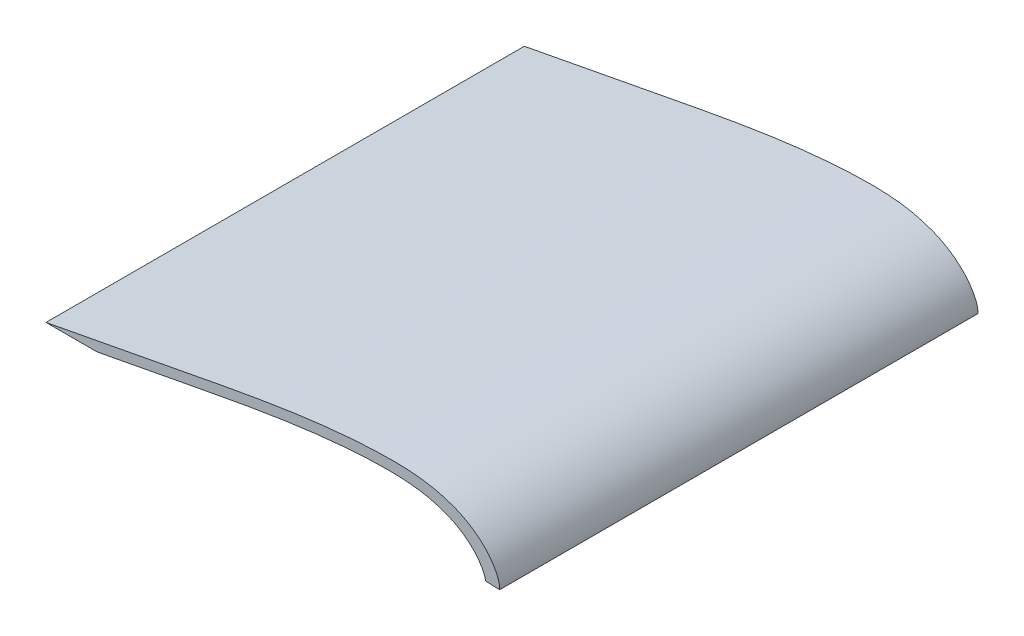
SolidWorks part; units mm, degrees
ref_plane "Front Plane" through (0, 0, 0) normal (0, 0, 1) x (1, 0, 0)
ref_plane "Top Plane" through (0, 0, 0) normal (0, 1, 0) x (1, 0, 0)
ref_plane "Right Plane" through (0, 0, 0) normal (1, 0, 0) x (0, 0, -1)
sketch "Sketch3" plane through (0, 0, 0) normal (0, 0, 1) x (1, 0, 0)
  line L0 (-35.4155, 0.9786) -> (-46.127, 0.9786)
  line L1 (45.7527, 0.1003) -> (48.7207, 0)
  line L2 (48.7207, 0) -> (-34.4545, 0) construction
  spline S0 degree 3 poles (48.7207, 0) (48.7413, 1.212) (48.0464, 2.8572) (46.8151, 4.7839) (45.4925, 6.3024) (43.8268, 7.7408) (41.4946, 9.2643) (38.1681, 10.7172) (33.7887, 11.8315) (28.7294, 12.2559) (23.717, 12.2188) (17.039, 11.8576) (8.6903, 10.9743) (-1.3041, 9.4479) (-11.2877, 7.6112) (-21.2786, 5.6967) (-34.613, 3.1689) (-44.6124, 1.2656) (-51.2793, 0) knots 0 0 0 0 0.032627 0.049883 0.064276 0.089251 0.111668 0.142584 0.191136 0.23834 0.285329 0.332382 0.426847 0.521876 0.617364 0.713023 0.808682 1 1 1 1
  spline S1 degree 3 poles (-35.4155, 0.9786) (-31.9007, 1.6464) (-28.3857, 2.3126) (-21.3563, 3.6489) (-17.8426, 4.3227) (-10.8123, 5.6541) (-7.2961, 6.3141) (-0.2462, 7.5388) (3.2897, 8.1009) (10.3826, 9.0556) (13.9397, 9.4499) (19.2948, 9.846) (21.0805, 9.9456) (24.6541, 10.0538) (26.4418, 10.0626) (29.1266, 9.9312) (30.0211, 9.8625) (31.7935, 9.6561) (32.6728, 9.5176) (34.415, 9.1542) (35.2779, 8.9305) (36.5587, 8.5235) (36.9845, 8.3756) (37.8235, 8.0564) (38.6499, 7.7134) (39.4456, 7.3119) (40.2226, 6.8751) (40.6019, 6.6392) (41.343, 6.1342) (41.7066, 5.8644) (42.4051, 5.299) (42.7404, 5.0027) (43.379, 4.3788) (43.6829, 4.0517) (44.2484, 3.3563) (44.5091, 2.9837) (44.8649, 2.4053) (44.978, 2.2096) (45.194, 1.8126) (45.2964, 1.6111) (45.4811, 1.1971) (45.5636, 0.9838) (45.6906, 0.5499) (45.7355, 0.3285) (45.7527, 0.1003) knots 0 0 0 0 0.125 0.125 0.25 0.25 0.375 0.375 0.5 0.5 0.625 0.625 0.6875 0.6875 0.75 0.75 0.78125 0.78125 0.8125 0.8125 0.84375 0.84375 0.859375 0.859375 0.875 0.890625 0.890625 0.90625 0.90625 0.921875 0.921875 0.9375 0.9375 0.953125 0.953125 0.96875 0.96875 0.976562 0.976562 0.984375 0.984375 0.992188 0.992188 1 1 1 1
  point P6 (0, 0)
extrude "Boss-Extrude1" add sketch "Sketch3" along normal mid plane 100 contours L0 S1 L1 S0 region at (-40.7712, 1.9349, 0)
sketch "Sketch4" plane through (0, 0, 0) normal (0, 1, 0) x (1, 0, 0)
  line L0 (48.7207, -50) -> (48.7207, 50) construction
  line L1 (48.7207, -50) -> (48.7207, 50)
  line L2 (48.7207, 0) -> (-13.2793, 0) construction
  circle A0 centre (-13.2793, 0) radius 4.9
  dimension "D1" = 9.8
  dimension "D2" = 62
extrude "Boss-Extrude2" add sketch "Sketch4" along normal up to surface and the other way blind 0.46 contours A0 region at (-13.2793, 0, 0) up to face at (-15.1234, 0.759, 0)
sketch "Sketch5" plane through (0, 0, 0) normal (0, 0, 1) x (1, 0, 0)
  line L1 (-8.3793, -0.46) -> (-8.3793, 6.1015) construction
  line L2 (-8.3793, -0.46) -> (-8.3793, 6.1015)
  line L3 (-18.1793, 4.2563) -> (-18.1793, -0.46) construction
  line L4 (-18.1793, 4.2563) -> (-18.1793, -0.46)
  spline S1 degree 3 poles (-525.0903, -2862.9343) (-687.8734, -106.1956) (-354.8821, -59.7534) (-21.3563, 3.6489) (-17.8426, 4.3227) (-10.8123, 5.6541) (-7.2961, 6.3141) (-0.2462, 7.5388) (3.2897, 8.1009) (10.3826, 9.0556) (13.9397, 9.4499) (19.2948, 9.846) (21.0805, 9.9456) (24.6541, 10.0538) (26.4418, 10.0626) (29.1266, 9.9312) (30.0211, 9.8625) (31.7935, 9.6561) (32.6728, 9.5176) (34.415, 9.1542) (35.2779, 8.9305) (36.5587, 8.5235) (36.9845, 8.3756) (37.8235, 8.0564) (38.6499, 7.7134) (39.4456, 7.3119) (40.2226, 6.8751) (40.6019, 6.6392) (41.343, 6.1342) (41.7066, 5.8644) (42.4051, 5.299) (42.7404, 5.0027) (43.379, 4.3788) (43.6829, 4.0517) (44.2484, 3.3563) (44.5091, 2.9837) (44.8649, 2.4053) (44.978, 2.2096) (45.194, 1.8126) (45.2964, 1.6111) (45.4811, 1.1971) (45.5636, 0.9838) (49.8278, -13.5819) (-27.1275, -47.71) (-2855.9649, -752.5254) knots -11.611785 -11.611785 -11.611785 -11.611785 0.125 0.125 0.25 0.25 0.375 0.375 0.5 0.5 0.625 0.625 0.6875 0.6875 0.75 0.75 0.78125 0.78125 0.8125 0.8125 0.84375 0.84375 0.859375 0.859375 0.875 0.890625 0.890625 0.90625 0.90625 0.921875 0.921875 0.9375 0.9375 0.953125 0.953125 0.96875 0.96875 0.976562 0.976562 0.984375 0.984375 0.992188 0.992188 1.508965 1.508965 1.508965 1.508965 only from (-35.4155, 0.9786) to (45.7527, 0.1003) construction
  spline S2 degree 3 poles (-35.4155, 0.9786) (-31.9007, 1.6464) (-28.3857, 2.3126) (-21.3563, 3.6489) (-17.8426, 4.3227) (-10.8123, 5.6541) (-7.2961, 6.3141) (-0.2462, 7.5388) (3.2897, 8.1009) (10.3826, 9.0556) (13.9397, 9.4499) (19.2948, 9.846) (21.0805, 9.9456) (24.6541, 10.0538) (26.4418, 10.0626) (29.1266, 9.9312) (30.0211, 9.8625) (31.7935, 9.6561) (32.6728, 9.5176) (34.415, 9.1542) (35.2779, 8.9305) (36.5587, 8.5235) (36.9845, 8.3756) (37.8235, 8.0564) (38.6499, 7.7134) (39.4456, 7.3119) (40.2226, 6.8751) (40.6019, 6.6392) (41.343, 6.1342) (41.7066, 5.8644) (42.4051, 5.299) (42.7404, 5.0027) (43.379, 4.3788) (43.6829, 4.0517) (44.2484, 3.3563) (44.5091, 2.9837) (44.8649, 2.4053) (44.978, 2.2096) (45.194, 1.8126) (45.2964, 1.6111) (45.4811, 1.1971) (45.5636, 0.9838) (45.6906, 0.5499) (45.7355, 0.3285) (45.7527, 0.1003) knots 0 0 0 0 0.125 0.125 0.25 0.25 0.375 0.375 0.5 0.5 0.625 0.625 0.6875 0.6875 0.75 0.75 0.78125 0.78125 0.8125 0.8125 0.84375 0.84375 0.859375 0.859375 0.875 0.890625 0.890625 0.90625 0.90625 0.921875 0.921875 0.9375 0.9375 0.953125 0.953125 0.96875 0.96875 0.976562 0.976562 0.984375 0.984375 0.992188 0.992188 1 1 1 1
  point P0 (-18.1793, 4.2563)
  point P1 (-18.1793, -0.46)
  point P5 (-8.3793, -0.46)
  dimension "D1" = 6.5615
  dimension "D2" = 4.7163
sketch "Sketch6" plane through (0, 0, 0) normal (0, 0, 1) x (1, 0, 0)
  line L0 (-18.1793, -0.46) -> (-8.3793, -0.46) construction
  line L1 (-18.1793, -0.46) -> (-8.3793, -0.46)
  line L2 (-13.2793, -0.46) -> (-13.2793, 3.54)
  line L3 (-13.2793, 3.54) -> (-10.2793, 3.54)
  line L4 (-10.2793, 3.54) -> (-10.2793, 1.54)
  line L5 (-10.2793, 1.54) -> (-11.7793, 1.54)
  line L6 (-11.7793, 1.54) -> (-11.7793, -0.46)
  point P2 (-13.2793, -0.46)
  dimension "D1" = 1.5
  dimension "D2" = 2
  dimension "D3" = 3
  dimension "D4" = 2
revolve "Cut-Revolve1" cut sketch "Sketch6" angle 360 about L2 region at (-12.0293, 1.8733, 0)
sketch "Sketch7" plane through (0, 0, 0) normal (0, 0, 1) x (1, 0, 0)
  line L0 (-18.1793, -0.46) -> (-8.3793, -0.46) construction
  line L1 (-18.1793, -0.46) -> (-8.3793, -0.46)
  line L2 (-13.2793, -0.46) -> (-13.2793, 1.54) construction
  line L3 (-16.2793, 1.54) -> (-10.2793, 1.54)
  line L4 (-14.2793, 0.54) -> (-12.2793, 0.54) construction
  line L5 (-14.2793, 1.54) -> (-14.2793, -0.46)
  line L6 (-12.2793, 1.54) -> (-12.2793, -0.46)
  line L7 (-16.2793, 1.54) -> (-16.2793, 3.04)
  line L8 (-16.2793, 3.04) -> (-10.2793, 3.04)
  line L9 (-10.2793, 3.04) -> (-10.2793, 1.54)
  point P7 (-13.2793, 1.54)
  point P10 (-13.2793, 0.54)
  dimension "D1" = 2
  dimension "D2" = 6
  dimension "D3" = 2
  dimension "D4" = 1.5
ref_plane "Plane1" through (-13.2793, 0, 0) normal (1, 0, 0) x (0, 0, -1)
sketch "Sketch8" plane through (-13.2793, 0, 0) normal (1, 0, 0) x (0, 0, -1)
  line L0 (-1.5, -0.46) -> (1.5, -0.46) construction
  line L1 (-1.5, -0.46) -> (1.5, -0.46)
  line L2 (-3, 3.54) -> (3, 3.54)
  line L3 (-3, 3.54) -> (3, 3.54) construction
  line L4 (-3, 3.54) -> (-3, 1.54)
  line L5 (3, 1.54) -> (-3, 1.54) construction
  line L6 (-3, 1.54) -> (-1, 1.54)
  line L7 (-1, 1.54) -> (-1, -0.46)
  line L8 (-1, -0.46) -> (1, -0.46)
  line L9 (1, -0.46) -> (1, 1.54)
  line L10 (1, 1.54) -> (3, 1.54)
  line L11 (3, 1.54) -> (3, 3.54)
  line L12 (1, 0.7183) -> (-1, 0.7183) construction
  line L14 (0, -0.46) -> (0, 1.54) construction
  point P17 (0, 0.7183)
  point P20 (0, 0)
  dimension "D1" = 2
  dimension "D2" = 2
extrude "Cut-Extrude2" cut sketch "Sketch8" against normal blind 5 contours L10 L11 L2 L4 L6 L7 L1 L9 region at (-13.2793, 2.04, 0)
sketch "Sketch13" plane through (0, 0, 50) normal (0, 0, 1) x (1, 0, 0)
  line L1 (45.7527, 0.1003) -> (48.7207, 0) construction
  line L2 (45.7527, 0.1003) -> (48.7207, 0)
sketch "Sketch14" plane through (0, 0, 50) normal (0, 0, 1) x (1, 0, 0)
  spline S0 degree 3 poles (-2870.1927, -688.3452) (26.4309, -61.9171) (59.7941, -15.5258) (46.8151, 4.7839) (45.4925, 6.3024) (43.8268, 7.7408) (41.4946, 9.2643) (38.1681, 10.7172) (33.7887, 11.8315) (28.7294, 12.2559) (23.717, 12.2188) (17.039, 11.8576) (8.6903, 10.9743) (-1.3041, 9.4479) (-11.2877, 7.6112) (-21.2786, 5.6967) (-506.1884, -86.23) (-984.3764, -194.629) (-1935.2759, 2100.805) knots -0.613276 -0.613276 -0.613276 -0.613276 0.032627 0.049883 0.064276 0.089251 0.111668 0.142584 0.191136 0.23834 0.285329 0.332382 0.426847 0.521876 0.617364 0.713023 0.808682 14.532028 14.532028 14.532028 14.532028 only from (48.7207, 0) to (-51.2793, 0) construction
  spline S1 degree 3 poles (48.7207, 0) (48.7413, 1.212) (48.0464, 2.8572) (46.8151, 4.7839) (45.4925, 6.3024) (43.8268, 7.7408) (41.4946, 9.2643) (38.1681, 10.7172) (33.7887, 11.8315) (28.7294, 12.2559) (23.717, 12.2188) (17.039, 11.8576) (8.6903, 10.9743) (-1.3041, 9.4479) (-11.2877, 7.6112) (-21.2786, 5.6967) (-34.613, 3.1689) (-44.6124, 1.2656) (-51.2793, 0) knots 0 0 0 0 0.032627 0.049883 0.064276 0.089251 0.111668 0.142584 0.191136 0.23834 0.285329 0.332382 0.426847 0.521876 0.617364 0.713023 0.808682 1 1 1 1
